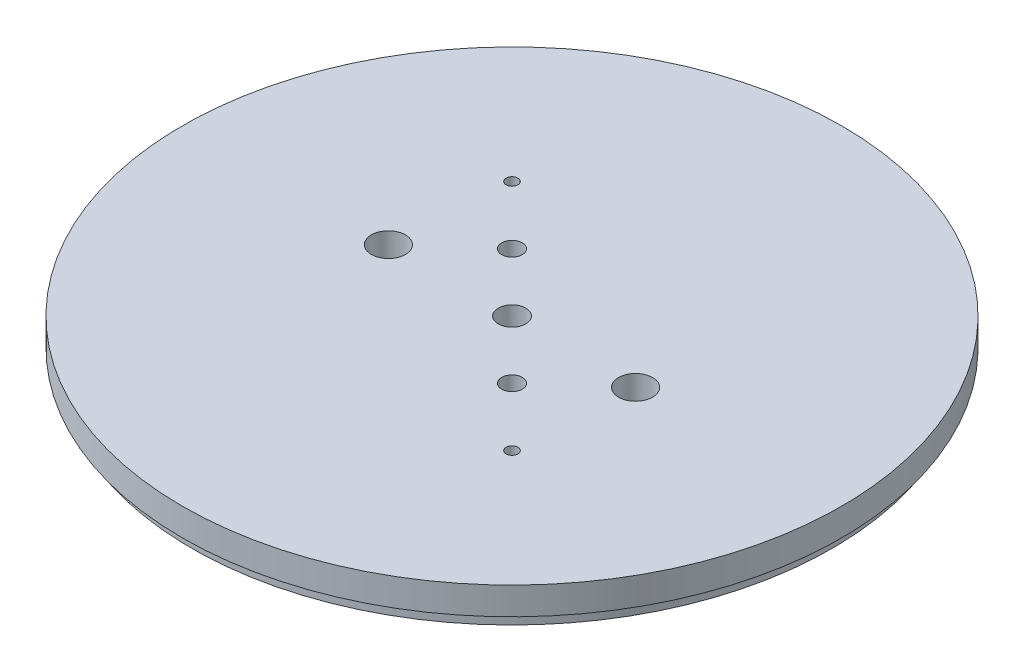
SolidWorks part; units mm, degrees
ref_plane "Front Plane" through (0, 0, 0) normal (0, 0, 1) x (1, 0, 0)
ref_plane "Top Plane" through (0, 0, 0) normal (0, 1, 0) x (1, 0, 0)
ref_plane "Right Plane" through (0, 0, 0) normal (1, 0, 0) x (0, 0, -1)
sketch "Sketch1" plane through (0, 0, 0) normal (0, 1, 0) x (1, 0, 0)
  line L0 (0, -76.2) -> (0, 76.2) construction
  line L1 (-76.2, 0) -> (76.2, 0) construction
  line L2 (-26.9408, 26.9408) -> (0, 0) construction
  line L3 (0, 56.7387) -> (0, 29.6936) construction
  line L4 (3.6407, 56.7387) -> (3.6407, 29.6936) construction
  line L5 (-3.6407, 56.7387) -> (-3.6407, 29.6936) construction
  line L6 (0, -56.7387) -> (0, -29.6936) construction
  line L7 (3.6407, -56.7387) -> (3.6407, -29.6936) construction
  line L8 (-3.6407, -56.7387) -> (-3.6407, -29.6936) construction
  line L9 (-53.8815, -53.8815) -> (54.3236, 54.3236) construction
  circle A0 centre (0, 0) radius 76.2
  circle A1 centre (0, 0) radius 3.175
  circle A2 centre (28.575, 0) radius 3.937
  circle A3 centre (-28.575, 0) radius 3.937
  circle A4 centre (-26.9408, 26.9408) radius 1.3589
  arc A6 (3.6407, 56.7387) -> (-3.6407, 56.7387) centre (0, 56.7387) ccw construction
  arc A7 (-3.6407, 29.6936) -> (3.6407, 29.6936) centre (0, 29.6936) ccw construction
  arc A8 (3.6407, -56.7387) -> (-3.6407, -56.7387) centre (0, -56.7387) cw construction
  arc A9 (-3.6407, -29.6936) -> (3.6407, -29.6936) centre (0, -29.6936) cw construction
  circle A10 centre (26.9408, -26.9408) radius 1.3589
  circle A11 centre (-13.4704, 13.4704) radius 2.3813
  circle A12 centre (13.4704, -13.4704) radius 2.3813
  point P16 (0, 43.2162)
  point P19 (0, 0)
  point P26 (0, -43.2162)
  dimension "D1" = 152.4
  dimension "D2" = 6.35
  dimension "D3" = 7.874
  dimension "D5" = 2.7178
  dimension "D8" = 4.7625
  dimension "D6" = 38.1
  dimension "D7" = 45
  dimension "D4" = 45
  dimension "D9" = 28.575
extrude "Boss-Extrude1" add sketch "Sketch1" along normal blind 9.525
sketch "Sketch2" plane through (0, 0, 0) normal (0, -1, 0) x (1, 0, 0)
  circle A0 centre (0, 0) radius 76.2
  circle A1 centre (0, 0) radius 74.041
  dimension "D1" = 152.4
  dimension "D2" = 148.082
extrude "Cut-Extrude1" cut sketch "Sketch2" against normal blind 3.175
sketch "Sketch3" plane through (0, 9.525, 0) normal (0, 1, 0) x (1, 0, 0)
  line L0 (0, 76.2) -> (0, -76.2) construction
  line L1 (-76.2, 0) -> (76.2, 0) construction
  line L2 (0, 34.798) -> (0, 13.97) construction
  line L3 (3.2385, 34.798) -> (3.2385, 13.97)
  line L4 (-3.2385, 34.798) -> (-3.2385, 13.97)
  line L5 (0, -34.798) -> (0, -13.97) construction
  line L6 (3.2385, -34.798) -> (3.2385, -13.97)
  line L7 (-3.2385, -34.798) -> (-3.2385, -13.97)
  circle A0 centre (0, 0) radius 76.2 construction
  arc A1 (3.2385, 34.798) -> (-3.2385, 34.798) centre (0, 34.798) ccw
  arc A2 (-3.2385, 13.97) -> (3.2385, 13.97) centre (0, 13.97) ccw
  arc A3 (3.2385, -34.798) -> (-3.2385, -34.798) centre (0, -34.798) cw
  arc A4 (-3.2385, -13.97) -> (3.2385, -13.97) centre (0, -13.97) cw
  point P7 (0, 13.97)
  point P8 (0, 34.798)
  point P12 (0, 24.384)
  point P20 (0, -24.384)
  point P25 (0, -34.798)
  point P26 (0, -13.97)
  dimension "D1" = 13.97
  dimension "D2" = 20.828
  dimension "D3" = 6.477
extrude "Cut-Extrude2" cut sketch "Sketch3" against normal blind 3.556 from offset 5.969 offset against normal yes
equation "\"leadDist\"=1.5"
equation "\"Lead_Screw_Dist\" = 2.25in"
equation "\"D9@Sketch1\"=\"Lead_Screw_Dist\"/2"
